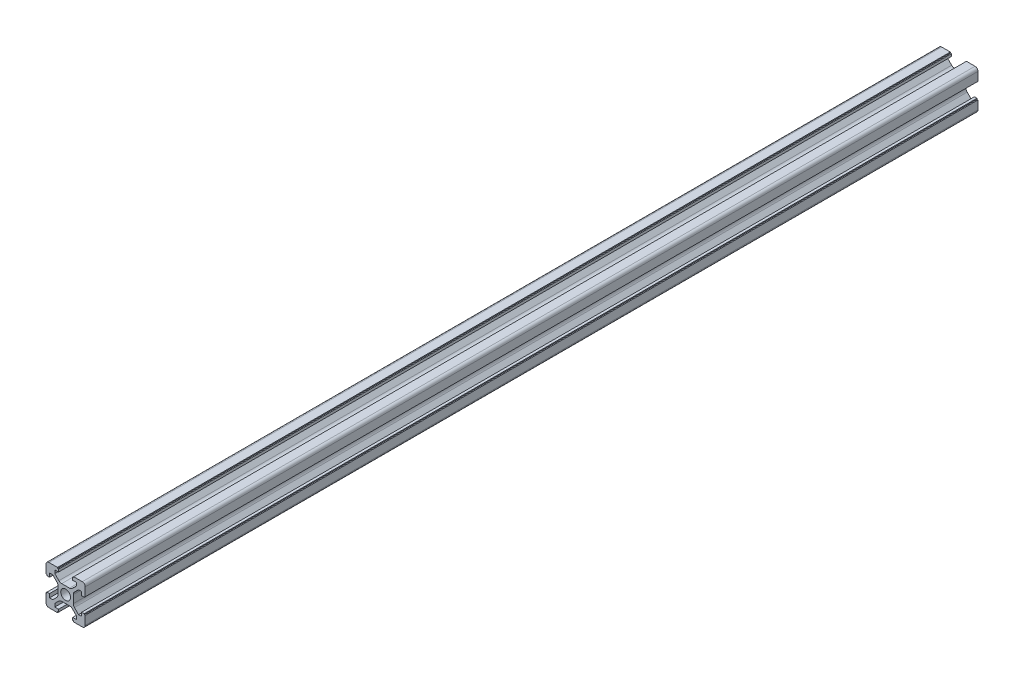
SolidWorks part; units mm, degrees
material "6063-O"
ref_plane "Front Plane" through (0, 0, 0) normal (0, 0, 1) x (1, 0, 0)
ref_plane "Top Plane" through (0, 0, 0) normal (0, 1, 0) x (1, 0, 0)
ref_plane "Right Plane" through (0, 0, 0) normal (1, 0, 0) x (0, 0, -1)
sketch "Sketch1" plane through (0, 0, 0) normal (0, 0, 1) x (1, 0, 0)
  line L0 (10, -4.1) -> (10, -8.5)
  line L1 (4.1, 10) -> (8.5, 10)
  line L2 (8.5, -10) -> (4.1, -10)
  line L3 (-8.5, -10) -> (-4.1, -10)
  line L4 (10, 8.5) -> (10, 4.1)
  line L7 (8.5, 10) -> (4.1, 10)
  line L8 (5.5, 6.5607) -> (3.4251, 4.4858)
  line L9 (8.5, 10) -> (4.1, 10)
  line L10 (3.9, 2.0109) -> (3.9, -2.0109)
  line L11 (2.0109, -3.9) -> (-2.0109, -3.9)
  line L12 (-3.9, -2.0109) -> (-3.9, 2.0109)
  line L13 (-2.0109, 3.9) -> (2.8393, 3.9)
  line L14 (2.5, 0) -> (22.2403, 0) construction
  line L15 (3.6, 9.5) -> (3.6, 8.2)
  line L16 (9.5, 3.6) -> (8.2, 3.6)
  line L17 (8.2, 3.6) -> (8.2, 5.5)
  line L18 (8.2, 5.5) -> (6.5607, 5.5)
  line L19 (10, -4.1) -> (10, -8.5)
  line L20 (4.1, 9.5) -> (3.6, 9.5)
  line L21 (4.1, 10) -> (4.1, 9.5)
  line L22 (8.5, 10) -> (4.1, 10)
  line L23 (10, 4.1) -> (9.5, 4.1)
  line L24 (9.5, 4.1) -> (9.5, 3.6)
  line L25 (5.5, 8.2) -> (5.5, 6.5607)
  line L26 (3.6, 8.2) -> (5.5, 8.2)
  line L27 (4.4858, 3.4251) -> (6.5607, 5.5)
  line L28 (10, -8.5) -> (10, -4.1)
  line L29 (6.5607, -5.5) -> (4.4858, -3.4251)
  line L30 (10, -8.5) -> (10, -4.1)
  line L31 (2.0109, -3.9) -> (-2.0109, -3.9)
  line L32 (3.9, 2.8393) -> (3.9, -2.0109)
  line L33 (9.5, -3.6) -> (8.2, -3.6)
  line L34 (3.6, -9.5) -> (3.6, -8.2)
  line L35 (3.6, -8.2) -> (5.5, -8.2)
  line L36 (5.5, -8.2) -> (5.5, -6.5607)
  line L37 (9.5, -4.1) -> (9.5, -3.6)
  line L38 (10, -4.1) -> (9.5, -4.1)
  line L39 (10, -8.5) -> (10, -4.1)
  line L40 (4.1, -10) -> (4.1, -9.5)
  line L41 (4.1, -9.5) -> (3.6, -9.5)
  line L42 (8.2, -5.5) -> (6.5607, -5.5)
  line L43 (8.2, -3.6) -> (8.2, -5.5)
  line L44 (3.4251, -4.4858) -> (5.5, -6.5607)
  line L45 (-4.1, -10) -> (-8.5, -10)
  line L46 (-10, -8.5) -> (-10, -4.1)
  line L47 (-8.5, -10) -> (-4.1, -10)
  line L48 (-5.5, -6.5607) -> (-3.4251, -4.4858)
  line L49 (-8.5, -10) -> (-4.1, -10)
  line L50 (-3.9, -2.0109) -> (-3.9, 2.0109)
  line L51 (2.0109, -3.9) -> (-2.0109, -3.9)
  line L52 (-3.6, -9.5) -> (-3.6, -8.2)
  line L53 (-9.5, -3.6) -> (-8.2, -3.6)
  line L54 (-8.2, -3.6) -> (-8.2, -5.5)
  line L55 (-8.2, -5.5) -> (-6.5607, -5.5)
  line L56 (-4.1, -9.5) -> (-3.6, -9.5)
  line L57 (-4.1, -10) -> (-4.1, -9.5)
  line L58 (-8.5, -10) -> (-4.1, -10)
  line L59 (-10, -4.1) -> (-9.5, -4.1)
  line L60 (-9.5, -4.1) -> (-9.5, -3.6)
  line L61 (-5.5, -8.2) -> (-5.5, -6.5607)
  line L62 (-3.6, -8.2) -> (-5.5, -8.2)
  line L63 (-4.4858, -3.4251) -> (-6.5607, -5.5)
  line L64 (-10, 4.1) -> (-10, 8.5)
  line L65 (-8.5, 10) -> (-4.1, 10)
  line L66 (-10, 8.5) -> (-10, 4.1)
  line L67 (-6.5607, 5.5) -> (-4.4858, 3.4251)
  line L68 (-10, 8.5) -> (-10, 4.1)
  line L69 (-2.0109, 3.9) -> (2.0109, 3.9)
  line L70 (-3.9, -2.0109) -> (-3.9, 2.0109)
  line L71 (-9.5, 3.6) -> (-8.2, 3.6)
  line L72 (-3.6, 9.5) -> (-3.6, 8.2)
  line L73 (-3.6, 8.2) -> (-5.5, 8.2)
  line L74 (-5.5, 8.2) -> (-5.5, 6.5607)
  line L75 (-9.5, 4.1) -> (-9.5, 3.6)
  line L76 (-10, 4.1) -> (-9.5, 4.1)
  line L77 (-10, 8.5) -> (-10, 4.1)
  line L78 (-4.1, 10) -> (-4.1, 9.5)
  line L79 (-4.1, 9.5) -> (-3.6, 9.5)
  line L80 (-8.2, 5.5) -> (-6.5607, 5.5)
  line L81 (-8.2, 3.6) -> (-8.2, 5.5)
  line L82 (-3.4251, 4.4858) -> (-5.5, 6.5607)
  line L83 (4.1, -10) -> (8.5, -10)
  arc A0 (2.0109, -3.9) -> (3.4251, -4.4858) centre (2.0109, -5.9) cw
  arc A1 (4.4858, -3.4251) -> (3.9, -2.0109) centre (5.9, -2.0109) cw
  arc A2 (3.9, 2.0109) -> (4.4858, 3.4251) centre (5.9, 2.0109) cw
  arc A3 (2.0109, 3.9) -> (3.4251, 4.4858) centre (2.0109, 5.9) ccw
  arc A4 (-2.0109, 3.9) -> (-3.4251, 4.4858) centre (-2.0109, 5.9) cw
  arc A5 (-4.4858, 3.4251) -> (-3.9, 2.0109) centre (-5.9, 2.0109) cw
  arc A6 (-3.4251, -4.4858) -> (-2.0109, -3.9) centre (-2.0109, -5.9) cw
  arc A7 (-3.9, -2.0109) -> (-4.4858, -3.4251) centre (-5.9, -2.0109) cw
  circle A8 centre (0, 0) radius 2.5
  arc A9 (-8.5, -10) -> (-10, -8.5) centre (-8.5, -8.5) cw
  arc A10 (-10, 8.5) -> (-8.5, 10) centre (-8.5, 8.5) cw
  arc A11 (8.5, 10) -> (10, 8.5) centre (8.5, 8.5) cw
  arc A12 (8.5, -10) -> (10, -8.5) centre (8.5, -8.5) ccw
  point P0 (0, 0)
  point P86 (0, 0)
  point P107 (10, -10)
  dimension "D3" = 2
  dimension "D5" = 5
  dimension "D2" = 1.5
  dimension "D8" = 1.5
  dimension "D6" = 4
  dimension "D7" = 6.1
  dimension "D11" = 0.5
  dimension "D12" = 0.5
extrude "Boss-Extrude2" add sketch "Sketch1" along normal blind 455 contours L2 A12 L0 L38 L37 L33 L43 L42 L29 A1 L10 A2 L27 L18 L17 L16 L24 L23 L4 A11 L1 L21 L20 L15 L26 L25 L8 A3 L13 A4 L82 L74 L73 L72 L79 L78 L65 A10 L64 L76 L75 L71 L81 L80 L67 A5 L12 region at (9.7172, -6.3, 0)
